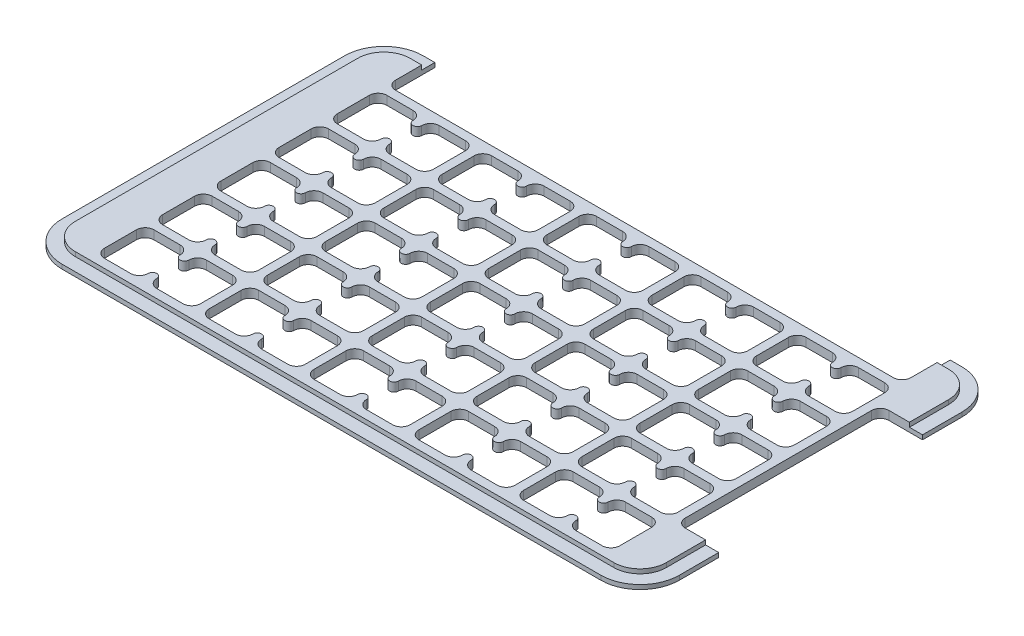
SolidWorks part; units mm, degrees
ref_plane "Front Plane" through (0, 0, 0) normal (0, 0, 1) x (1, 0, 0)
ref_plane "Top Plane" through (0, 0, 0) normal (0, 1, 0) x (1, 0, 0)
ref_plane "Right Plane" through (0, 0, 0) normal (1, 0, 0) x (0, 0, -1)
sketch "Sketch1" plane through (0, 0, 0) normal (0, 1, 0) x (1, 0, 0)
  line L1 (-106, -62) -> (106, -62)
  line L2 (-106, -62) -> (-106, 62)
  line L3 (-106, 62) -> (106, 62)
  line L4 (106, -62) -> (106, 62)
  line L5 (-106, -62) -> (106, 62) construction
  line L6 (-106, 62) -> (106, -62) construction
  point P0 (0, 0)
  dimension "D1" = 212
  dimension "D2" = 124
extrude "Outer Profile" add sketch "Sketch1" along normal blind 1.5
sketch "Sketch2" plane through (0, 1.5, 0) normal (0, 1, 0) x (1, 0, 0)
  line L1 (-101.5, -57.5) -> (101.5, -57.5)
  line L2 (-101.5, -57.5) -> (-101.5, 57.5)
  line L3 (-101.5, 57.5) -> (101.5, 57.5)
  line L4 (101.5, -57.5) -> (101.5, 57.5)
  line L5 (-101.5, -57.5) -> (101.5, 57.5) construction
  line L6 (-101.5, 57.5) -> (101.5, -57.5) construction
  point P0 (0, 0)
  dimension "D1" = 203
  dimension "D2" = 115
extrude "Inner Profile" add sketch "Sketch2" along normal blind 1.5
fillet "Fillet1" radius 9 4 edges at (101.5, 2.25, 57.5) (101.5, 2.25, -57.5) (-101.5, 2.25, -57.5) (-101.5, 2.25, 57.5)
fillet "Fillet2" radius 13.5 4 edges at (-106, 0.75, -62) (106, 0.75, -62) (106, 0.75, 62) (-106, 0.75, 62)
sketch "Sketch3" plane through (0, 3, 0) normal (0, 1, 0) x (1, 0, 0)
  line L1 (-90.5, -56.5) -> (90.5, -56.5) construction
  line L2 (-90.5, -56.5) -> (-90.5, 56.5) construction
  line L3 (-90.5, 56.5) -> (90.5, 56.5) construction
  line L4 (90.5, -56.5) -> (90.5, 56.5) construction
  line L5 (-90.5, -56.5) -> (90.5, 56.5) construction
  line L6 (-90.5, 56.5) -> (90.5, -56.5) construction
  point P0 (0, 0)
  dimension "D1" = 181
  dimension "D2" = 113
sketch "Sketch4" plane through (0, 3, 0) normal (0, 1, 0) x (1, 0, 0)
  line L1 (-88.5, 45.5) -> (88.5, 45.5)
  line L2 (-88.5, 45.5) -> (-88.5, 62)
  line L3 (-88.5, 62) -> (88.5, 62)
  line L4 (88.5, 45.5) -> (88.5, 62)
  line L5 (0, 45.5) -> (0, 0) construction
  line L6 (-90.5, 56.5) -> (90.5, -56.5) construction
  line L7 (92.5, 62) -> (-92.5, 62) construction
  line L8 (106, -48.5) -> (106, 48.5) construction
  line L9 (91.5, -35) -> (106, -35)
  line L10 (-90.5, 56.5) -> (90.5, 56.5) construction
  line L11 (91.5, -35) -> (91.5, 35)
  line L12 (91.5, 35) -> (106, 35)
  line L13 (106, -35) -> (106, 35)
  line L14 (91.5, -35) -> (106, 35) construction
  line L15 (91.5, 35) -> (106, -35) construction
  line L17 (90.5, -56.5) -> (90.5, 56.5) construction
  point P10 (98.75, 0)
  dimension "D1" = 70
  dimension "D2" = 11
  dimension "D3" = 177
  dimension "D4" = 1
extrude "Message Bar" cut sketch "Sketch4" against normal through all
sketch "Sketch5" plane through (0, 3, 0) normal (0, 1, 0) x (1, 0, 0)
  line L1 (-13.5, -54.5) -> (-4.5, -54.5)
  line L2 (-16.5, -51.5) -> (-16.5, -40.5)
  line L3 (-13.5, -37.5) -> (-4.5, -37.5)
  line L4 (-1.5, -51.5) -> (-1.5, -40.5)
  line L5 (-9, -37.5) -> (-9, -54.5) construction
  line L6 (0, 0) -> (0, -37.3494) construction
  line L7 (-90.5, -56.5) -> (90.5, 56.5) construction
  line L8 (-90.5, -56.5) -> (90.5, -56.5) construction
  arc A0 (-4.5, -54.5) -> (-1.5, -51.5) centre (-4.5, -51.5) ccw
  arc A1 (-13.5, -54.5) -> (-16.5, -51.5) centre (-13.5, -51.5) cw
  arc A2 (-4.5, -37.5) -> (-1.5, -40.5) centre (-4.5, -40.5) cw
  arc A3 (-16.5, -40.5) -> (-13.5, -37.5) centre (-13.5, -40.5) cw
  point P15 (-1.5, -54.5)
  point P18 (-16.5, -54.5)
  point P23 (-16.5, -37.5)
  dimension "D4" = 3
  dimension "D1" = 15
  dimension "D2" = 17
  dimension "D3" = 9
  dimension "D5" = 2
extrude "Cutout" cut sketch "Sketch5" against normal through all
pattern_linear "Cutouts" count 5 spacing 18 along (-1, 0, 0) count 5 spacing 20 along (0, 0, -1) of "Cutout"
mirror "Mirror Cutouts" about plane through (0, 0, 0) normal (1, 0, 0) of "Cutouts"
fillet "Corner Rad" radius 3 4 edges at (88.5, 1.5, -45.5) (-88.5, 1.5, -45.5) (91.5, 1.5, 35) (91.5, 1.5, -35)
sketch "Sketch6" plane through (0, 3, 0) normal (0, 1, 0) x (1, 0, 0)
  line L0 (-73.5, 28.5) -> (-73.5, 39.5) construction
  line L1 (-73.5, 39.5) -> (-73.5, 28.5)
  line L2 (-70.5, 39.5) -> (-70.5, 28.5)
  arc A0 (-73.5, 39.5) -> (-70.5, 39.5) centre (-72, 39.5) ccw
  arc A3 (-73.5, 28.5) -> (-70.5, 28.5) centre (-72, 28.5) cw
extrude "Opening" cut sketch "Sketch6" against normal through all
pattern_linear "Openings" count 5 spacing 36 along (1, 0, 0) count 5 spacing 20 along (0, 0, 1) of "Opening"
